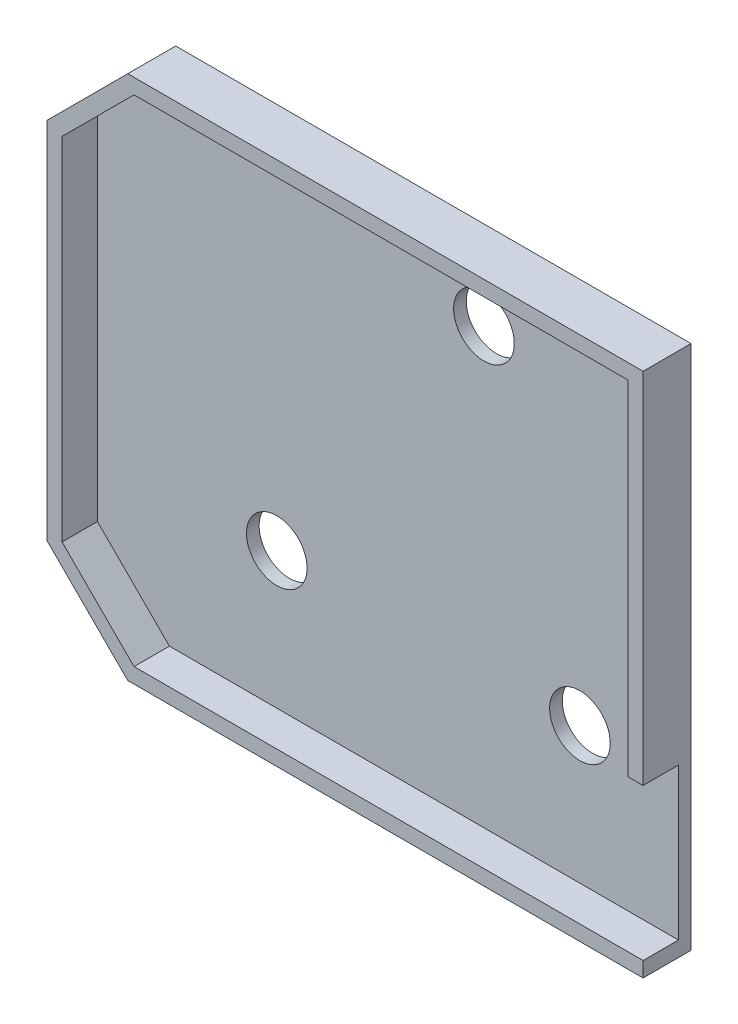
SolidWorks part; units mm, degrees
ref_plane "Plan de face" through (0, 0, 0) normal (0, 0, 1) x (1, 0, 0)
ref_plane "Plan de dessus" through (0, 0, 0) normal (0, 1, 0) x (1, 0, 0)
ref_plane "Plan de droite" through (0, 0, 0) normal (1, 0, 0) x (0, 0, -1)
sketch "Esquisse1" plane through (0, 0, 0) normal (0, 0, 1) x (1, 0, 0)
  line L0 (0, -85) -> (16, -101)
  line L4 (118, 3) -> (118, -101)
  line L5 (16, 3) -> (0, -13)
  line L7 (118, 3) -> (16, 3)
  line L8 (0, -13) -> (0, -85)
  line L9 (16, -101) -> (118, -101)
  dimension "D1" = 104
  dimension "D2" = 118
  dimension "D3" = 16
  dimension "D4" = 16
  dimension "D5" = 16
  dimension "D6" = 16
extrude "Boss.-Extru.1" add sketch "Esquisse1" along normal blind 2.5
sketch "Esquisse2" plane through (0, 0, 2.5) normal (0, 0, 1) x (1, 0, 0)
  line L0 (0, -13) -> (0, -85) construction
  line L1 (3, 0) -> (115, 0) construction
  line L2 (3, 0) -> (3, -98) construction
  line L3 (3, -98) -> (115, -98) construction
  line L4 (115, 0) -> (115, -98) construction
  line L5 (16, -101) -> (118, -101) construction
  line L6 (118, -101) -> (118, 3) construction
  line L7 (118, 3) -> (16, 3) construction
  line L9 (3, -83.7574) -> (17.2426, -98)
  line L10 (0, -85) -> (16, -101) construction
  line L11 (3, -14.2426) -> (17.2426, 0)
  line L12 (16, 3) -> (0, -13) construction
  line L13 (115, 0) -> (17.2426, 0)
  line L14 (3, -14.2426) -> (3, -83.7574)
  line L15 (17.2426, -98) -> (115, -98)
  line L16 (118, 3) -> (118, -101) construction
  line L17 (118, -101) -> (16, -101)
  line L18 (16, -101) -> (0, -85)
  line L19 (0, -85) -> (0, -13)
  line L20 (0, -13) -> (16, 3)
  line L21 (16, 3) -> (118, 3)
  line L30 (118, -2.5) -> (118, 3)
  line L31 (115, -98) -> (118, -98)
  line L32 (118, -98) -> (118, -101)
  line L33 (115, 0) -> (115, -68)
  line L34 (115, -68) -> (118, -68)
  line L35 (118, -68) -> (118, -2.5)
  point P24 (116.5, -98)
  dimension "D1" = 3
  dimension "D2" = 3
  dimension "D3" = 3
  dimension "D4" = 3
  dimension "D5" = 3
  dimension "D6" = 3
  dimension "D7" = 30
extrude "Boss.-Extru.2" add sketch "Esquisse2" along normal blind 7
sketch "Esquisse3" plane through (0, 0, 2.5) normal (0, 0, 1) x (1, 0, 0)
  line L0 (118, -98) -> (17.2426, -98) construction
  line L1 (17.2426, 0) -> (115, 0) construction
  line L2 (115, 0) -> (115, -68) construction
  line L3 (3, -83.7574) -> (3, -14.2426) construction
  circle A0 centre (98.5, -71) radius 6
  circle A1 centre (79.5, -12) radius 6
  circle A2 centre (38.5, -71) radius 6
  dimension "D1" = 27
  dimension "D2" = 27
  dimension "D3" = 12
  dimension "D4" = 16.5
  dimension "D5" = 35.5
  dimension "D6" = 35.5
extrude "Enlèv. mat.-Extru.1" cut sketch "Esquisse3" against normal blind 10
